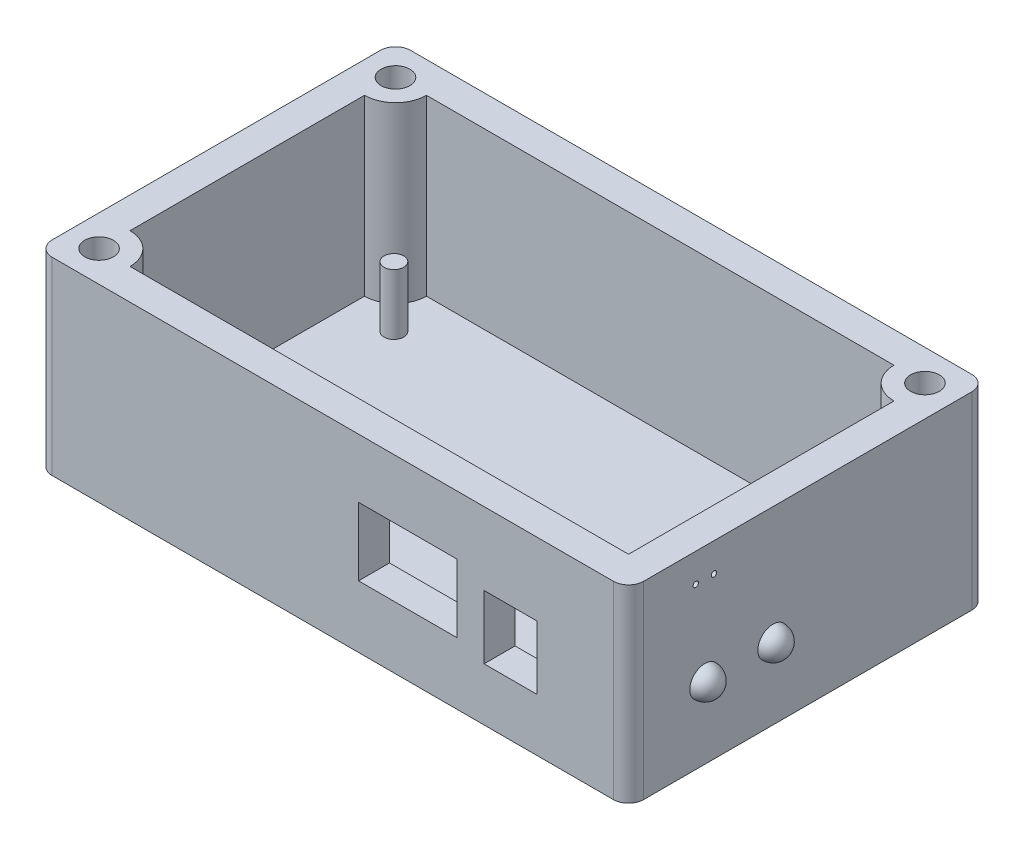
SolidWorks part; units mm, degrees
other "Markup1"
sketch "Sketch5" plane through (62.5, 42, 52.5) normal (0.8956, 0.4441, 0.0259) x (-0.0234, 0.1051, -0.9942)
ref_plane "Front Plane" through (0, 0, 0) normal (0, 0, 1) x (1, 0, 0)
ref_plane "Top Plane" through (0, 0, 0) normal (0, 1, 0) x (1, 0, 0)
ref_plane "Right Plane" through (0, 0, 0) normal (1, 0, 0) x (0, 0, -1)
sketch "Sketch1" plane through (0, 0, 0) normal (0, 1, 0) x (1, 0, 0)
  line L0 (0, 0) -> (0, 34.5863) construction
  line L1 (37.4485, -22.225) -> (-37.4485, -22.225) construction
  line L2 (37.4485, -22.225) -> (37.4485, 22.225) construction
  line L3 (37.4485, 22.225) -> (-37.4485, 22.225) construction
  line L5 (37.4485, -22.225) -> (-37.4485, 22.225) construction
  line L6 (37.4485, 22.225) -> (-37.4485, -22.225) construction
  line L11 (-39.2492, 0) -> (44.45, 0) construction
  line L12 (-44.45, 19.685) -> (-39.2492, 19.685) construction
  line L13 (-50.8, 0) -> (50.8, 0) construction
  line L14 (-37.4485, -22.225) -> (-37.4485, -34.5863) construction
  line L15 (0, 34.5863) -> (0, -34.5863) construction
  line L16 (37.4485, 22.225) -> (37.4485, 34.5863) construction
  line L17 (37.4485, 34.5863) -> (37.4485, -34.5863) construction
  line L18 (-37.4485, -22.225) -> (-50.8, -22.225) construction
  line L19 (-50.8, -22.225) -> (50.8, -22.225) construction
  line L20 (-37.4485, 22.225) -> (-50.8, 22.225) construction
  line L21 (-50.8, 22.225) -> (50.8, 22.225) construction
  line L22 (-37.4485, 22.225) -> (-55.4884, 29.0808) construction
  line L71 (-49.6508, 24.8858) -> (-49.6508, 30.0866)
  line L76 (-49.6508, 30.0866) -> (-44.45, 30.0866)
  line L77 (44.45, 30.0866) -> (-44.45, 30.0866)
  line L78 (49.6508, 24.8858) -> (49.6508, -24.8858)
  line L79 (-49.6508, 24.8858) -> (-49.6508, -24.8858)
  line L80 (44.45, -30.0866) -> (-44.45, -30.0866)
  line L82 (-37.4485, 22.225) -> (37.4485, 22.225) construction
  line L84 (-37.4485, -22.225) -> (37.4485, -22.225) construction
  line L85 (37.4485, 22.225) -> (37.4485, -22.225) construction
  line L86 (44.45, -30.0866) -> (49.6508, -30.0866)
  line L87 (49.6508, -30.0866) -> (49.6508, -24.8858)
  line L89 (-44.45, 24.8858) -> (-44.45, 19.685) construction
  line L91 (-44.45, 24.8858) -> (-39.2492, 24.8858) construction
  line L93 (-39.2492, 24.8858) -> (39.2492, 24.8858)
  line L95 (-44.45, 19.685) -> (-44.45, -19.685)
  line L97 (49.6508, 30.0866) -> (44.45, 30.0866)
  line L98 (49.6508, 24.8858) -> (49.6508, 30.0866)
  line L99 (44.45, 19.685) -> (44.45, -19.685)
  line L101 (-39.2492, -24.8858) -> (39.2492, -24.8858)
  line L102 (-49.6508, -30.0866) -> (-44.45, -30.0866)
  line L103 (-49.6508, -24.8858) -> (-49.6508, -30.0866)
  line L106 (49.6508, -30.0866) -> (-49.6508, -30.0866)
  line L107 (49.6508, -30.0866) -> (49.6508, 30.0866)
  line L108 (49.6508, 30.0866) -> (-49.6508, 30.0866)
  line L109 (-49.6508, -30.0866) -> (-49.6508, 30.0866)
  line L110 (49.6508, -30.0866) -> (-49.6508, 30.0866) construction
  line L111 (49.6508, 30.0866) -> (-49.6508, -30.0866) construction
  line L112 (39.2492, -24.8858) -> (44.45, -24.8858)
  line L113 (44.45, -24.8858) -> (44.45, -19.685)
  line L115 (-39.2492, 24.8858) -> (-39.2492, -24.8858) construction
  line L118 (44.45, 19.685) -> (-39.2492, 19.685) construction
  line L119 (44.45, -24.8858) -> (41.9146, -24.8858) construction
  line L120 (44.45, -24.8858) -> (44.45, -21.2016) construction
  line L123 (44.45, -24.8858) -> (40.5358, -24.8858)
  line L124 (44.45, -24.8858) -> (44.45, -22.225)
  line L125 (44.45, -22.225) -> (40.5358, -22.225) construction
  line L126 (40.5358, -24.8858) -> (40.5358, -22.225) construction
  line L127 (-39.2492, 19.685) -> (-39.2492, -24.8858) construction
  line L128 (2.667, 19.685) -> (2.667, -22.225) construction
  line L129 (39.2492, -24.8858) -> (39.2492, 19.685) construction
  line L130 (39.2492, -2.6004) -> (-39.2492, -2.6004) construction
  circle A1 centre (-44.45, 24.8858) radius 2.413
  arc A8 (-49.6508, 24.8858) -> (-44.45, 30.0866) centre (-44.45, 24.8858) cw construction
  arc A9 (44.45, 30.0866) -> (49.6508, 24.8858) centre (44.45, 24.8858) cw construction
  arc A10 (-49.6508, -24.8858) -> (-44.45, -30.0866) centre (-44.45, -24.8858) ccw construction
  arc A11 (-39.2492, 24.8858) -> (-44.45, 19.685) centre (-44.45, 24.8858) cw
  circle A12 centre (44.45, 24.8858) radius 2.413
  arc A13 (39.2492, 24.8858) -> (44.45, 19.685) centre (44.45, 24.8858) ccw
  arc A16 (-39.2492, -24.8858) -> (-44.45, -19.685) centre (-44.45, -24.8858) ccw
  circle A17 centre (-44.45, -24.8858) radius 2.413
  circle A19 centre (42.1868, -22.225) radius 1.651
  circle A20 centre (42.1868, 17.0242) radius 1.651
  circle A21 centre (-36.8528, -22.225) radius 1.651
  circle A22 centre (-36.8528, 17.0242) radius 1.651
  point P0 (0, 0)
  point P6 (0, 0)
  point P40 (0, 24.8858)
  point P42 (0, 30.0866)
  point P46 (-49.6508, 0)
  point P49 (49.6508, 0)
  point P54 (-41.0641, 30.216)
  point P57 (44.45, 0)
  point P62 (-44.45, 0)
  dimension "D6" = 4.826
  dimension "D3" = 3.302
  dimension "D1" = 88.9
  dimension "D2" = 39.37
  dimension "D4" = 41.783
extrude "Boss-Extrude1" add sketch "Sketch1" along normal blind 29.21 contours A1 | L79 L103 L102 L80 L86 L87 L78 L98 L97 L77 L76 L71 L101 A16 L95 A11 L93 A13 L99 A12 A1 A17 | A17 | A12 region at (-48.4897, 0, -27.4862) region at (-44.45, 0, -24.8858) region at (44.45, 0, -24.8858) region at (-44.45, 0, 24.8858)
extrude "Boss-Extrude2" add sketch "Sketch1<23>" against normal blind 2.54 contours L79 L103 L102 L80 L86 L87 L78 L98 L97 L77 L76 L71 L101 A16 L95 A11 L93 A13 L99 A12 A1 A17 | A17 | A1 | A12 | A16 L101 L112 L113 L99 A13 L93 A11 L95 A22 A20 A19 A21 | A20 | A19 | A21 | A22 region at (-48.4897, 0, -27.4862) region at (0.1863, 0, 0.0908) region at (-44.45, 0, -24.8858) region at (44.45, 0, -24.8858) region at (-44.45, 0, 24.8858) region at (42.1868, 0, 22.225) region at (42.1868, 0, -17.0242) region at (-36.8528, 0, 22.225) region at (-36.8528, 0, -17.0242)
sketch "Sketch1<23>" plane through (0, 0, 0) normal (0, 1, 0) x (1, 0, 0) same geometry as "Sketch1"
extrude "Cut-Extrude1" cut sketch "Sketch1<25>" against normal blind 12.192 from surface contours A12 | A1 | A17 starting at face at (-5.4532, 29.21, -2.6583)
sketch "Sketch1<25>" plane through (0, 0, 0) normal (0, 1, 0) x (1, 0, 0) same geometry as "Sketch1"
extrude "Boss-Extrude5" add sketch "Sketch1<28>" along normal blind 10.16 contours A20 | A21 | A22 | A19 region at (42.1868, 0, -17.0242) region at (-36.8528, 0, 22.225) region at (-36.8528, 0, -17.0242)
sketch "Sketch1<28>" plane through (0, 0, 0) normal (0, 1, 0) x (1, 0, 0) same geometry as "Sketch1"
sketch "Sketch6" plane through (0, 0, 24.8858) normal (0, 0, -1) x (-1, 0, 0)
  line L0 (-34.29, 29.21) -> (-34.29, 17.018) construction
  line L2 (39.2492, 29.21) -> (-44.45, 29.21) construction
  line L3 (-44.45, 29.21) -> (-44.45, 0) construction
  line L10 (-34.29, 17.018) -> (-25.4, 17.018)
  line L11 (-34.29, 17.018) -> (-34.29, 6.35)
  line L12 (-34.29, 6.35) -> (-25.4, 6.35)
  line L13 (-25.4, 17.018) -> (-25.4, 6.35)
  dimension "D1" = 12.192
  dimension "D2" = 10.16
  dimension "D3" = 10.668
  dimension "D4" = 8.89
extrude "Cut-Extrude2" cut sketch "Sketch6" against normal blind 10.16
sketch "Sketch8" plane through (0, 0, 30.0866) normal (0, 0, 1) x (1, 0, 0)
  line L0 (25.4, 6.35) -> (-6.4149, 6.35) construction
  line L1 (24.3325, 7.874) -> (-5.811, 7.874) construction
  line L2 (25.4, 6.35) -> (25.4, 17.018) construction
  line L3 (20.828, 7.874) -> (4.318, 7.874)
  line L4 (20.828, 7.874) -> (20.828, 19.304)
  line L5 (20.828, 19.304) -> (4.318, 19.304)
  line L6 (4.318, 7.874) -> (4.318, 19.304)
  dimension "D1" = 1.524
  dimension "D2" = 11.43
  dimension "D3" = 16.51
  dimension "D4" = 4.572
extrude "Cut-Extrude4" cut sketch "Sketch8" against normal blind 10.16
sketch "Sketch10" plane through (44.45, 0, 0) normal (-1, 0, 0) x (0, 0, 1)
  line L0 (-13.8633, 0) -> (18.2186, 0) construction
  line L1 (-19.685, 0) -> (19.685, 0) construction
  line L2 (19.2978, 9.5758) -> (7.8678, 9.5758) construction
  line L3 (24.8858, 29.21) -> (24.8858, 0) construction
  line L4 (17.2658, 9.5758) -> (19.2978, 9.5758) construction
  line L5 (5.8358, 9.5758) -> (7.8678, 9.5758) construction
  line L6 (5.8358, 7.5438) -> (5.8358, 0) construction
  circle A0 centre (17.2658, 9.5758) radius 2.032
  circle A1 centre (5.8358, 9.5758) radius 2.032
  dimension "D2" = 4.064
  dimension "D3" = 7.62
  dimension "D5" = 4.064
  dimension "D1" = 9.5758
  dimension "D4" = 11.43
extrude "Cut-Extrude7" cut sketch "Sketch10" against normal through all
sketch "Sketch12" plane through (49.6508, 0, 0) normal (1, 0, 0) x (0, 0, -1)
  line L0 (-17.2658, 12.1158) -> (-17.2658, 7.0358) construction
  line L1 (-17.2658, 11.6078) -> (-17.2658, 7.5438) construction
  line L2 (-17.2658, 9.5758) -> (-5.8358, 9.5758) construction
  line L3 (-11.5508, 12.7989) -> (-11.5508, 4.9832) construction
  line L4 (-17.2658, 12.1158) -> (-17.2658, 7.0358)
  line L5 (-5.8358, 12.1158) -> (-5.8358, 7.0358)
  circle A0 centre (-17.2658, 9.5758) radius 2.032 construction
  arc A3 (-17.2658, 12.1158) -> (-17.2658, 7.0358) centre (-17.2658, 9.5758) ccw
  arc A4 (-17.2658, 11.6078) -> (-17.2658, 7.5438) centre (-17.2658, 9.5758) ccw
  arc A5 (-5.8358, 11.6078) -> (-5.8358, 7.5438) centre (-5.8358, 9.5758) cw
  arc A6 (-5.8358, 12.1158) -> (-5.8358, 7.0358) centre (-5.8358, 9.5758) cw
  dimension "D2" = 2.54
  dimension "D1" = 2.032
revolve "Revolve1" add sketch "Sketch12" angle 180 about L4 region at (49.6508, 11.8618, 17.3226) reverse direction yes
revolve "Revolve2" add sketch "Sketch12<4>" angle 180 about L5 region at (49.6508, 9.5758, 3.3526)
sketch "Sketch12<4>" plane through (49.6508, 0, 0) normal (1, 0, 0) x (0, 0, -1) same geometry as "Sketch12"
sketch "Sketch13" plane through (49.6508, 0, 0) normal (1, 0, 0) x (0, 0, -1)
  line L0 (-19.8058, 9.5758) -> (-19.8058, 29.21) construction
  line L1 (-30.0866, 29.21) -> (30.0866, 29.21) construction
  line L2 (-3.2958, 9.5758) -> (-3.2958, 29.21) construction
  line L3 (-19.8058, 23.368) -> (-19.8058, 25.4) construction
  line L4 (-19.8058, 25.4) -> (-3.2958, 25.4) construction
  line L5 (-19.8058, 25.4) -> (-19.8058, 23.368) construction
  line L6 (-19.8058, 23.368) -> (-3.2958, 23.368) construction
  line L7 (-3.2958, 25.4) -> (-3.2958, 23.368) construction
  line L8 (-19.8058, 25.4) -> (-19.8058, 24.384) construction
  line L9 (-19.8058, 24.384) -> (-3.2958, 24.384) construction
  line L10 (-17.2658, 29.21) -> (-17.2658, 20.3788) construction
  circle A0 centre (-17.2658, 9.5758) radius 2.54 construction
  circle A1 centre (-5.8358, 9.5758) radius 2.54 construction
  circle A5 centre (-18.7898, 24.384) radius 1.016 construction
  circle A6 centre (-18.7898, 24.384) radius 0.45
  circle A7 centre (-15.7418, 24.384) radius 0.45
  circle A8 centre (-15.7418, 24.384) radius 1.016 construction
  dimension "D2" = 0.9
  dimension "D3" = 2.032
  dimension "D4" = 1.016
  dimension "D1" = 3.81
  dimension "D5" = 2.54
extrude "Cut-Extrude8" cut sketch "Sketch13" against normal blind 7.62
fillet "Fillet2" radius 2.54 4 edges at (-49.6508, 13.335, 30.0866) (-49.6508, 13.335, -30.0866) (49.6508, 13.335, -30.0866) (49.6508, 13.335, 30.0866)
